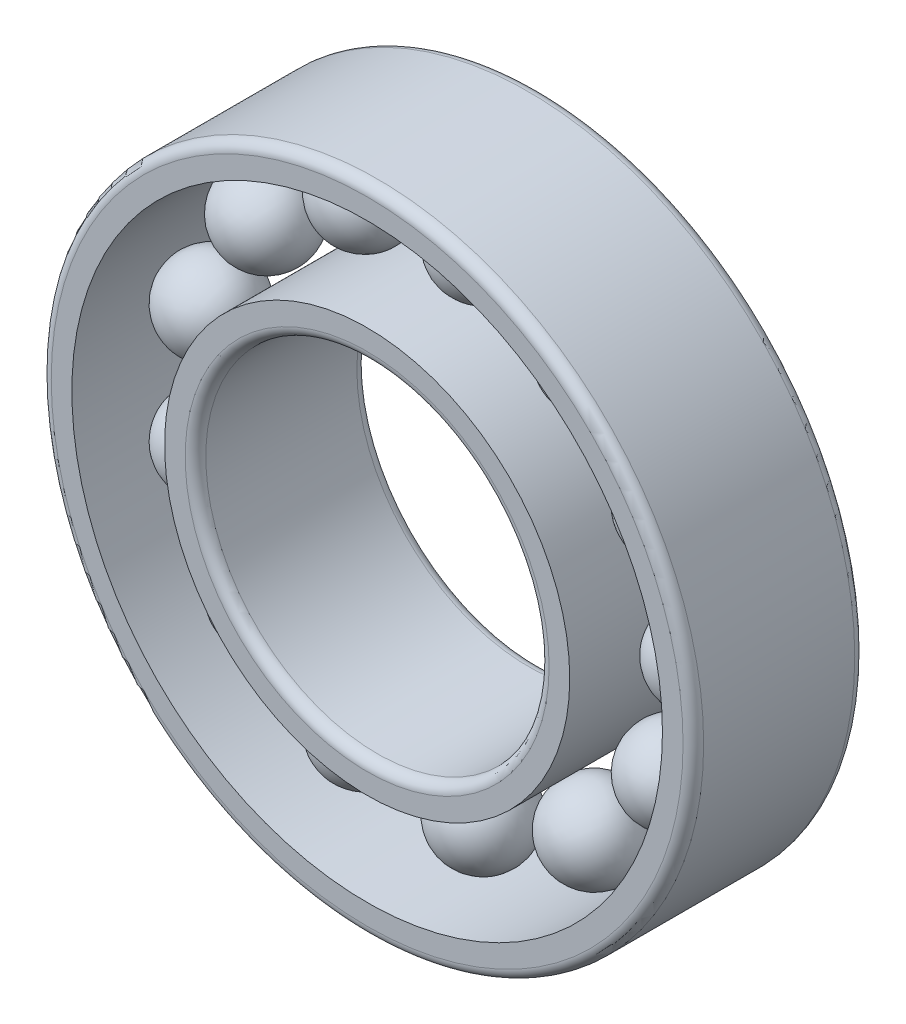
SolidWorks part; units mm, degrees
ref_plane "Front Plane" through (0, 0, 0) normal (0, 0, 1) x (1, 0, 0)
ref_plane "Top Plane" through (0, 0, 0) normal (0, 1, 0) x (1, 0, 0)
ref_plane "Right Plane" through (0, 0, 0) normal (1, 0, 0) x (0, 0, -1)
sketch "S" plane through (0, 0, 0) normal (0, 0, 1) x (1, 0, 0)
  line L0 (-2.5, 0) -> (2.5, 0) construction
  circle A0 centre (0, 0) radius 5 construction
  circle A1 centre (0, 0) radius 9.5 construction
  circle A2 centre (0, 0) radius 5.9 construction
  circle A3 centre (0, 0) radius 8.6 construction
  dimension "ID" = 10
  dimension "OD" = 19
  dimension "IDa" = 11.8
  dimension "ODa" = 17.2
  dimension "B" = 5
ref_axis "Z" through (0, 0, -2.75) along (0, 0, 1)
sketch "InnerS" plane through (0, 0, 0) normal (0, 1, 0) x (1, 0, 0)
  line L0 (5, -2.5) -> (5.9, -2.5)
  line L1 (5.9, -2.5) -> (5.9, 2.5)
  line L2 (5.9, 2.5) -> (5, 2.5)
  line L3 (5, 2.5) -> (5, -2.5)
  line L4 (0, -4.75) -> (0, 4.75) construction
  dimension "r1" = 5
  dimension "r2" = 5.9
  dimension "z1" = 2.5
  dimension "z2" = 2.5
revolve "InnerRing" add sketch "InnerS" angle 360 about L4
sketch "OuterS" plane through (0, 0, 0) normal (0, 1, 0) x (1, 0, 0)
  line L0 (8.6, -2.5) -> (9.5, -2.5)
  line L1 (9.5, -2.5) -> (9.5, 2.5)
  line L2 (9.5, 2.5) -> (8.6, 2.5)
  line L3 (8.6, 2.5) -> (8.6, -2.5)
  line L4 (0, -4.75) -> (0, 4.75) construction
  dimension "r1" = 8.6
  dimension "r2" = 9.5
  dimension "z1" = 2.5
  dimension "z2" = 2.5
revolve "OuterRing" add sketch "OuterS" angle 360 about L4
sketch "BallS" plane through (0, 0, 0) normal (0, 1, 0) x (1, 0, 0)
  line L0 (5.9675, 0) -> (8.5325, 0)
  arc A0 (5.9675, 0) -> (8.5325, 0) centre (7.25, 0) ccw
  dimension "r" = 1.2825
  dimension "p" = 7.25
revolve "Ball" add sketch "BallS" angle 360 about L0
pattern_circular "BallsPattern" count 13 over 360 about axis through (0, 0, -2.75) along (0, 0, 1) of bodies 103
fillet "F1" radius 0.3 2 edges at (9.5, 0, -2.5) (9.5, 0, 2.5)
fillet "F2" radius 0.3 2 edges at (5, 0, -2.5) (5, 0, 2.5)
equation "\"r1@InnerS\" = abs(0.5*\"ID@S\")"
equation "\"r2@InnerS\" = abs(0.5*\"IDa@S\")"
equation "\"z1@InnerS\" = abs(-0.5*\"B@S\")"
equation "\"z2@InnerS\" = abs(0.5*\"B@S\")"
equation "\"r1@OuterS\" = abs(0.5*\"ODa@S\")"
equation "\"r2@OuterS\" = abs(0.5*\"OD@S\")"
equation "\"z1@OuterS\" = abs(-0.5*\"B@S\")"
equation "\"z2@OuterS\" = abs(0.5*\"B@S\")"
equation "\"r@BallS\" = abs(0.2375*\"ODa@S\"-0.2375*\"IDa@S\")"
equation "\"p@BallS\" = abs(0.25*\"IDa@S\"+0.25*\"ODa@S\")"
equation "\"N@BallsPattern\" = int(2.417*(0.25*\"IDa@S\"+0.25*\"ODa@S\")/(0.2375*\"ODa@S\"-0.2375*\"IDa@S\"))"
equation "\"r_min@F2\" = \"r_min@F1\""
